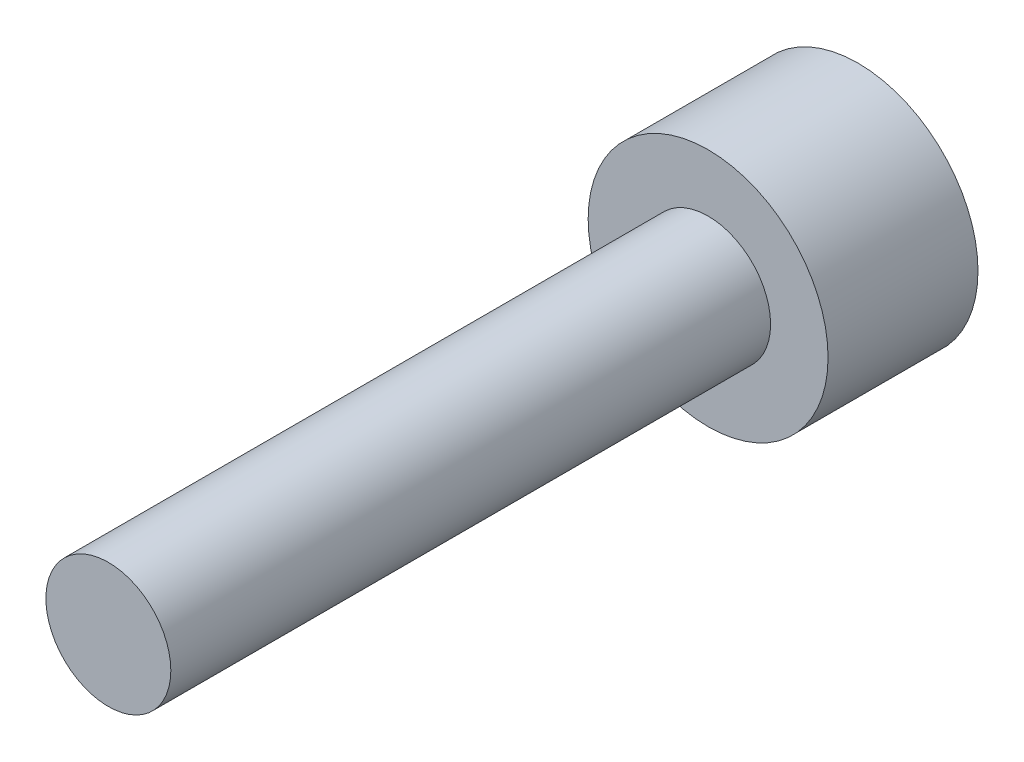
SolidWorks part; units mm, degrees
material "6061 Alloy"
ref_plane "Front Plane" through (0, 0, 0) normal (0, 0, 1) x (1, 0, 0)
ref_plane "Top Plane" through (0, 0, 0) normal (0, 1, 0) x (1, 0, 0)
ref_plane "Right Plane" through (0, 0, 0) normal (1, 0, 0) x (0, 0, -1)
sketch "Sketch1" plane through (0, 0, 0) normal (0, 0, 1) x (1, 0, 0)
  circle A0 centre (0, 0) radius 7.62
  circle A1 centre (0, 0) radius 3.9688
  dimension "D1" = 15.24
  dimension "D2" = 7.9375
extrude "Top Head" add sketch "Sketch1" along normal blind 9.525 contours A1 | A0 A1 region at (-7.4045, 0, 0) region at (0, 0, 0)
extrude "Lower Pin" add sketch "Sketch1<4>" along normal blind 41.275 from offset 6.35 contours A1 region at (0, 0, 0)
sketch "Sketch1<4>" plane through (0, 0, 0) normal (0, 0, 1) x (1, 0, 0) same geometry as "Sketch1"
sketch "Sketch2" plane through (0, 0, 0) normal (0, 0, -1) x (-1, 0, 0)
  circle A0 centre (0, 0) radius 3.175
  circle A1 centre (0, 0) radius 1.5875
  dimension "D1" = 6.35
extrude "O-Ring Opening" cut sketch "Sketch2" against normal blind 4.7625 contours A0 A1 | A1 region at (3.0852, 0, 0) region at (0, 0, 0)
extrude "POT Shaft Opening" cut sketch "Sketch2<3>" against normal blind 13.589 contours A1 region at (0, 0, 0)
sketch "Sketch2<3>" plane through (0, 0, 0) normal (0, 0, -1) x (-1, 0, 0) same geometry as "Sketch2"
